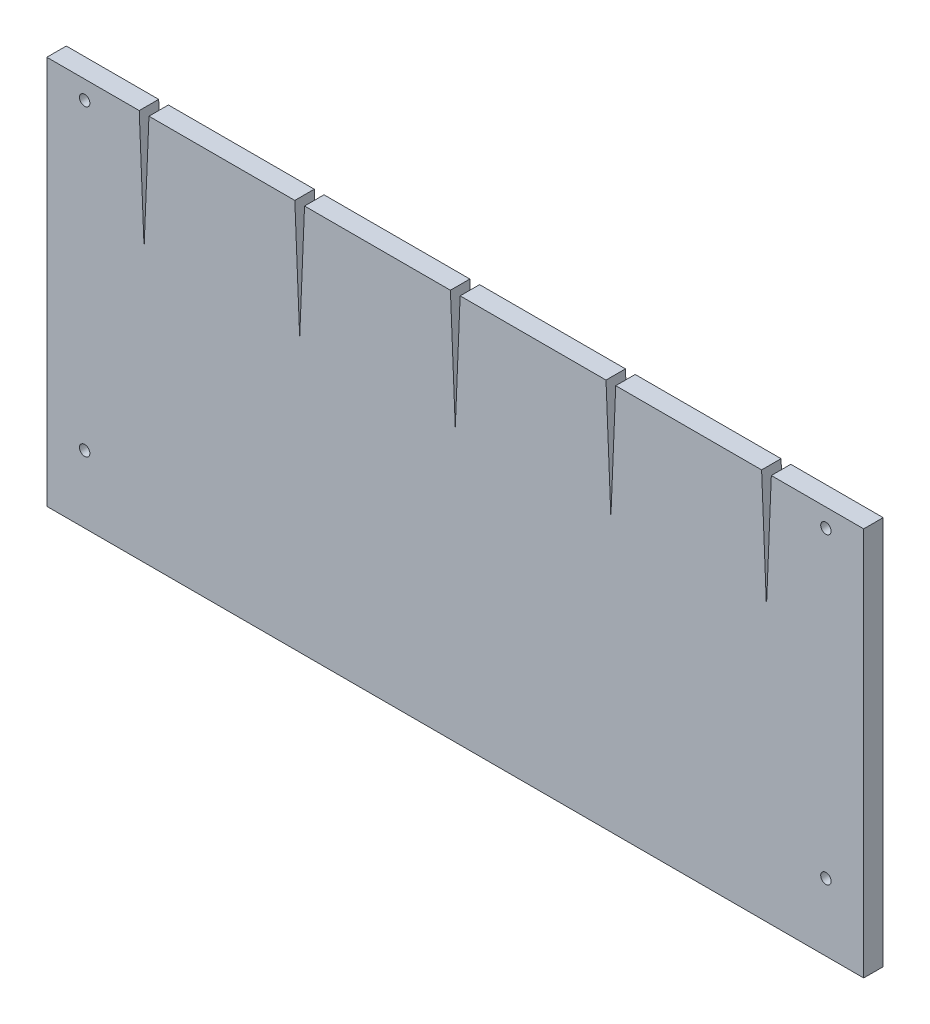
SolidWorks part; units mm, degrees
material "Acrylic (Medium-high impact)"
ref_plane "Front Plane" through (0, 0, 0) normal (0, 0, 1) x (1, 0, 0)
ref_plane "Top Plane" through (0, 0, 0) normal (0, 1, 0) x (1, 0, 0)
ref_plane "Right Plane" through (0, 0, 0) normal (1, 0, 0) x (0, 0, -1)
sketch "Sketch1" plane through (0, 0, 0) normal (0, 0, 1) x (1, 0, 0)
  line L1 (266.7, 127) -> (0, 127)
  line L2 (266.7, 127) -> (266.7, 0)
  line L3 (266.7, 0) -> (0, 0)
  line L4 (0, 127) -> (0, 0)
  line L5 (266.7, 127) -> (0, 0) construction
  line L6 (266.7, 0) -> (0, 127) construction
  point P0 (133.35, 63.5)
  dimension "D1" = 127
  dimension "D2" = 266.7
extrude "Boss-Extrude1" add sketch "Sketch1" along normal blind 6.35
hole_wizard "M3 Clearance Hole1" positions "Sketch2" profile "Sketch3" hole size "M3" standard "ANSI Metric" end condition through all
sketch "Sketch2" plane through (0, 0, 6.35) normal (0, 0, 1) x (1, 0, 0)
  line L0 (0, 127) -> (0, 0) construction
  line L1 (266.7, 127) -> (0, 127) construction
  line L2 (266.7, 0) -> (266.7, 127) construction
  line L3 (0, 0) -> (266.7, 0) construction
  point P0 (12.3444, 121.0056)
  point P2 (12.3444, 21.9964)
  point P4 (254.3556, 21.9964)
  point P6 (254.3556, 121.0056)
  dimension "D1" = 12.3444
  dimension "D2" = 5.9944
  dimension "D3" = 12.3444
  dimension "D4" = 21.9964
sketch "Sketch3" plane through (12.3444, 121.0056, 6.35) normal (1, 0, 0) x (0, -1, 0)
  line L0 (0, 0) -> (0, 6.35)
  line L1 (0, 6.35) -> (1.7, 6.35)
  line L2 (1.7, 6.35) -> (1.7, 0)
  line L5 (1.7, 0) -> (0, 0)
  line L11 (0, -6.35) -> (0, 107.95) construction
  dimension "Thru Hole Dia." = 3.4
  dimension "Thru Hole Depth" = 6.35
sketch "Sketch4" plane through (0, 0, 6.35) normal (0, 0, 1) x (1, 0, 0)
  line L0 (0, 127) -> (0, 0) construction
  line L1 (46.99, 107.95) -> (50.4952, 107.95)
  line L2 (46.99, 107.95) -> (46.99, 31.75)
  line L3 (46.99, 31.75) -> (50.4952, 31.75)
  line L4 (50.4952, 107.95) -> (50.4952, 31.75)
  line L5 (216.2048, 107.95) -> (219.71, 107.95)
  line L6 (216.2048, 107.95) -> (216.2048, 31.75)
  line L7 (216.2048, 31.75) -> (219.71, 31.75)
  line L8 (219.71, 107.95) -> (219.71, 31.75)
  line L9 (266.7, 0) -> (266.7, 127) construction
  line L10 (266.7, 127) -> (0, 127) construction
  dimension "D1" = 3.5052
  dimension "D2" = 76.2
  dimension "D3" = 46.99
  dimension "D4" = 46.99
  dimension "D5" = 19.05
extrude "Cut-Extrude1" [suppressed] cut sketch "Sketch4" against normal through all
sketch "Sketch5" plane through (0, 0, 6.35) normal (0, 0, 1) x (1, 0, 0)
  line L0 (0, 0) -> (266.7, 0)
  line L1 (266.7, 0) -> (266.7, 37.4822)
  line L2 (266.7, 0) -> (266.7, 127) construction
  line L3 (266.7, 37.4822) -> (0, 0)
  dimension "D1" = 8
extrude "Cut-Extrude2" [suppressed] cut sketch "Sketch5" against normal through all
sketch "Sketch6" plane through (0, 0, 6.35) normal (0, 0, 1) x (1, 0, 0)
  line L0 (30.1625, 127) -> (31.75, 88.9)
  line L1 (266.7, 127) -> (0, 127) construction
  line L2 (31.75, 88.9) -> (33.3375, 127)
  line L3 (33.3375, 127) -> (30.1625, 127)
  line L4 (0, 127) -> (0, 0) construction
  point P4 (31.75, 127)
  dimension "D1" = 38.1
  dimension "D2" = 3.175
  dimension "D3" = 31.75
extrude "Cut-Extrude3" cut sketch "Sketch6" against normal through all
pattern_linear "LPattern1" count 5 spacing 50.8 along (1, 0, 0) of "Cut-Extrude3"
